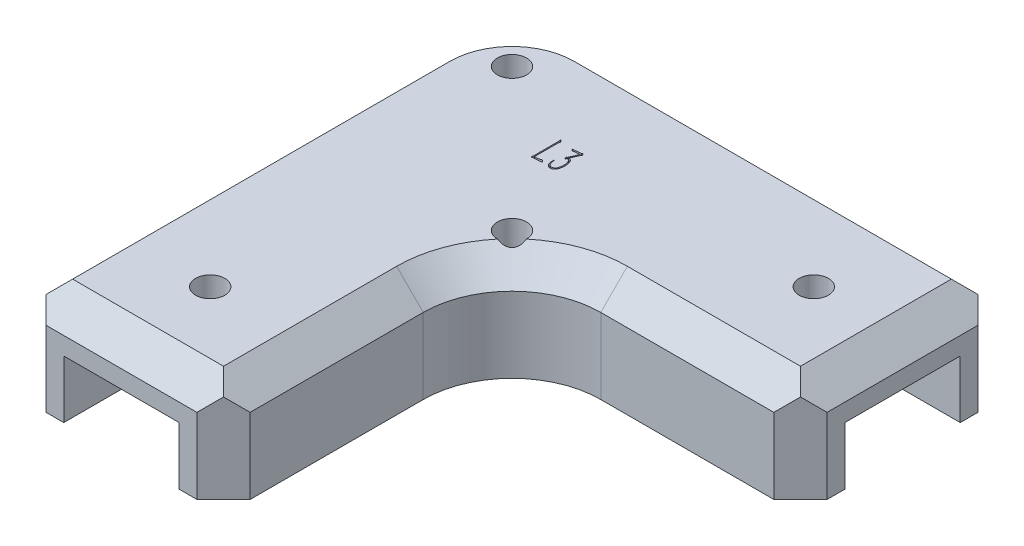
SolidWorks part; units mm, degrees
ref_plane "前视基准面" through (0, 0, 0) normal (0, 0, 1) x (1, 0, 0)
ref_plane "上视基准面" through (0, 0, 0) normal (0, 1, 0) x (1, 0, 0)
ref_plane "右视基准面" through (0, 0, 0) normal (1, 0, 0) x (0, 0, -1)
sketch "草图1" plane through (0, 0, 0) normal (0, 0, 1) x (1, 0, 0)
  line L1 (0, 0) -> (13, 0)
  line L2 (0, 0) -> (0, 13)
  line L3 (0, 13) -> (13, 13)
  line L4 (13, 0) -> (13, 13)
  line L5 (-5, 18) -> (18, 18)
  line L6 (-5, 18) -> (-5, -5)
  line L7 (-5, -5) -> (18, -5)
  line L8 (18, 18) -> (18, -5)
  dimension "D1" = 13
  dimension "D2" = 13
  dimension "D3" = 23
  dimension "D4" = 23
  dimension "D5" = 5
  dimension "D6" = 5
extrude "凸台-拉伸1" add sketch "草图1" along normal blind 55.5
sketch "草图2" plane through (0, -5, 0) normal (0, -1, 0) x (1, 0, 0)
  line L0 (-5, 55.5) -> (18, 55.5) construction
  line L1 (-5, 55.5) -> (-5, 0) construction
  circle A0 centre (6.5, 45.5) radius 1.65
  dimension "D1" = 3.3
  dimension "D2" = 10
  dimension "D3" = 11.5
extrude "切除-拉伸1" cut sketch "草图2" against normal blind 34
sketch "草图3" [suppressed] plane through (0, 25, 0) normal (0, 1, 0) x (1, 0, 0)
  line L0 (25, 0) -> (-5, 0) construction
  line L1 (2.5796, -2) -> (18.5796, -2)
  line L2 (2.5796, -2) -> (2.5796, -16)
  line L3 (2.5796, -16) -> (18.5796, -16)
  line L4 (18.5796, -2) -> (18.5796, -16)
  dimension "D1" = 14
  dimension "D2" = 2
  dimension "D3" = 16
sketch "草图4" plane through (18, 0, 0) normal (1, 0, 0) x (0, 0, -1)
  line L0 (-55.5, -5) -> (0, -5) construction
  line L1 (0, 18) -> (-23, 18)
  line L2 (0, 18) -> (0, -5)
  line L3 (0, -5) -> (-23, -5)
  line L4 (-23, 18) -> (-23, -5)
  circle A0 centre (-11.5, 6.5) radius 3
  dimension "D2" = 11.5
  dimension "D3" = 11.5
  dimension "D4" = 6
  dimension "D1" = 23
extrude "凸台-拉伸2" add sketch "草图4" along normal blind 22.5
sketch "草图5" plane through (40.5, 0, 0) normal (1, 0, 0) x (0, 0, -1)
  line L0 (0, -5) -> (0, 18) construction
  line L1 (-5, 0) -> (-18, 0)
  line L2 (-5, 0) -> (-5, 13)
  line L3 (-5, 13) -> (-18, 13)
  line L4 (-18, 0) -> (-18, 13)
  line L5 (-5, 0) -> (-18, 13) construction
  line L6 (-5, 13) -> (-18, 0) construction
  line L7 (-23, -5) -> (0, -5) construction
  point P0 (-11.5, 6.5)
  dimension "D1" = 13
  dimension "D2" = 13
  dimension "D3" = 5
  dimension "D4" = 5
extrude "拉伸-薄壁1" add sketch "草图5" along normal blind 10 thin thin type one direction wall 5
sketch "草图6" plane through (0, 18, 0) normal (0, 1, 0) x (1, 0, 0)
  line L0 (50.5, 0) -> (50.5, -23) construction
  line L1 (50.5, 0) -> (-5, 0) construction
  circle A0 centre (40.5, -11.5) radius 1.65
  dimension "D1" = 3.3
  dimension "D2" = 10
  dimension "D3" = 11.5
extrude "切除-拉伸2" cut sketch "草图6" against normal blind 39
sketch "草图7" plane through (40.5, 0, 0) normal (1, 0, 0) x (0, 0, -1)
  line L1 (-18, 13) -> (-5, 13)
  line L2 (-18, 13) -> (-18, 0)
  line L3 (-18, 0) -> (-5, 0)
  line L4 (-5, 13) -> (-5, 0)
extrude "切除-拉伸3" cut sketch "草图7" against normal blind 32
chamfer "倒角1" distance 3 angle 45 1 edges at (13, 6.5, 18)
chamfer "倒角2" [suppressed] distance 3 angle 45
sketch "草图8" plane through (0, -5, 0) normal (0, -1, 0) x (1, 0, 0)
  line L1 (-5, 55.5) -> (50.5, 55.5)
  line L2 (-5, 55.5) -> (-5, 0)
  line L3 (-5, 0) -> (50.5, 0)
  line L4 (50.5, 55.5) -> (50.5, 0)
extrude "切除-拉伸4" cut sketch "草图8" against normal blind 11.5
sketch "草图9" plane through (0, 13, 0) normal (0, -1, 0) x (1, 0, 0)
  line L0 (13, 5) -> (0, 18)
  line L2 (0, 18) -> (0, 0)
  line L3 (0, 0) -> (13, 0)
  line L4 (13, 0) -> (13, 5)
  dimension "D1" = 18
extrude "凸台-拉伸3" add sketch "草图9" along normal blind 6.5
fillet "圆角1" radius 10 1 edges at (-5, 12.25, 0)
fillet "圆角2" radius 10 1 edges at (18, 12.25, 23)
sketch "草图10" plane through (0, 6.5, 0) normal (0, -1, 0) x (1, 0, 0)
  line L0 (-5, 55.5) -> (-5, 10) construction
  line L1 (5, 0) -> (50.5, 0) construction
  line L2 (50.5, 18) -> (16, 18) construction
  line L3 (13, 21) -> (13, 55.5) construction
  circle A0 centre (2, 7) radius 1.65
  circle A1 centre (18, 23) radius 1.65
  dimension "D1" = 7
  dimension "D2" = 7
  dimension "D3" = 3.3
  dimension "D4" = 5
  dimension "D5" = 5
  dimension "D6" = 3.3
extrude "切除-拉伸5" cut sketch "草图10" against normal blind 28.5
chamfer "倒角3" distance 3 angle 45 6 edges at (18, 18, 44.25) (39.25, 18, 23) (20.9289, 18, 25.9289) (27.75, 18, 0) (-2.0711, 18, 2.9289) (-5, 18, 32.75)
chamfer "倒角4" distance 3 angle 45 2 edges at (50.5, 18, 11.5) (6.5, 18, 55.5)
chamfer "倒角5" distance 3 angle 45 4 edges at (50.5, 10.75, 0) (50.5, 10.75, 23) (18, 10.75, 55.5) (-5, 10.75, 55.5)
sketch "草图11" plane through (0, 18, 0) normal (0, 1, 0) x (1, 0, 0)
  text T0 "L3"
extrude "切除-拉伸6" cut sketch "草图11" against normal blind 0.3
